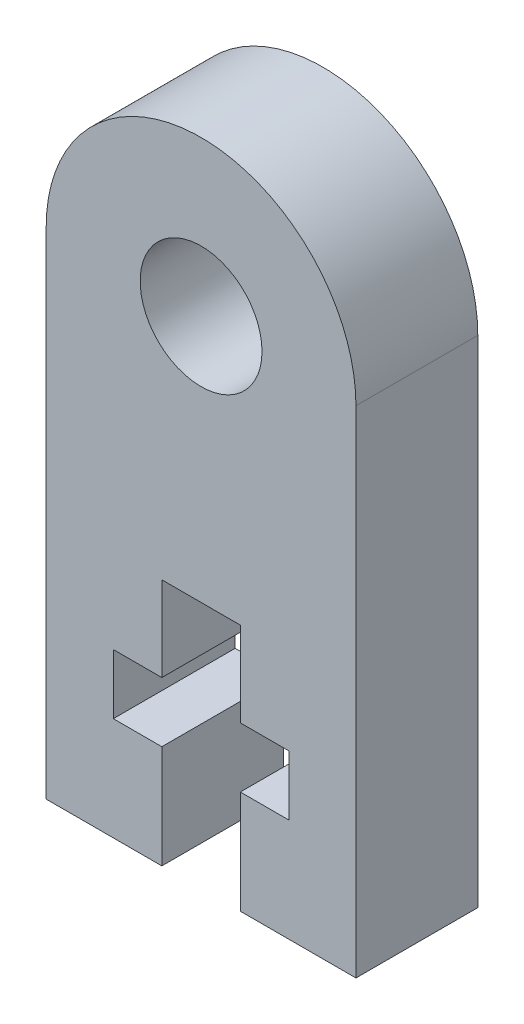
SolidWorks part; units mm, degrees
ref_plane "Front Plane" through (0, 0, 0) normal (0, 0, 1) x (1, 0, 0)
ref_plane "Top Plane" through (0, 0, 0) normal (0, 1, 0) x (1, 0, 0)
ref_plane "Right Plane" through (0, 0, 0) normal (1, 0, 0) x (0, 0, -1)
sketch "Sketch1" plane through (0, 0, 0) normal (0, 0, 1) x (1, 0, 0)
  line L0 (0, 0) -> (-2.086, 2.086) construction
  line L1 (0, 0) -> (0, 2.95) construction
  line L2 (-7.5, 0) -> (-7.5, -24)
  line L3 (-7.5, -24) -> (7.5, -24)
  line L4 (7.5, -24) -> (7.5, 0)
  line L5 (0, 0) -> (0, -24) construction
  circle A0 centre (0, 0) radius 2.95
  arc A1 (-7.5, 0) -> (7.5, 0) centre (0, 0) cw
  dimension "D1" = 5.9
  dimension "D4" = 45
  dimension "D5" = 24
  dimension "D6" = 15
extrude "Boss-Extrude1" add sketch "Sketch1" along normal blind 5.9
sketch "Sketch3" plane through (0, 0, 5.9) normal (0, 0, 1) x (1, 0, 0)
  line L0 (-7.5, -24) -> (7.5, -24) construction
  line L1 (-1.9, -24) -> (1.9, -24)
  line L2 (-1.9, -24) -> (-1.9, -19)
  line L3 (-1.9, -12) -> (1.9, -12)
  line L4 (1.9, -24) -> (1.9, -19)
  line L5 (0, -12) -> (0, 0) construction
  line L6 (1.9, -16.1) -> (4.25, -16.1)
  line L7 (-4.25, -16.1) -> (-1.9, -16.1)
  line L8 (-4.25, -16.1) -> (-4.25, -19)
  line L9 (-4.25, -19) -> (-1.9, -19)
  line L10 (4.25, -16.1) -> (4.25, -19)
  line L11 (-1.9, -16.1) -> (-1.9, -12)
  line L12 (1.9, -19) -> (4.25, -19)
  line L13 (1.9, -16.1) -> (1.9, -12)
  point P18 (-3.075, -19)
  dimension "D1" = 3.8
  dimension "D3" = 12
  dimension "D4" = 8.5
  dimension "D5" = 2.9
  dimension "D6" = 5
extrude "Cut-Extrude2" cut sketch "Sketch3" against normal through all
equation "\"smallPulleyTeeth\"= 15"
equation "\"largePulleyTeeth\"= 30"
equation "\"eighthThick\"= 2.9mm"
equation "\"sixteenthThick\" = 1.7mm"
equation "\"quarterThick\"=5.9mm"
equation "\"OD\" = 145mm"
equation "\"puckAngle\" = 60.5deg"
equation "\"puckDiam\" = 76.5mm"
equation "\"axlePress\" = 5.9mm"
equation "\"D1@Sketch1\"=\"axlePress\""
equation "\"D1@Boss-Extrude1\"=\"quarterThick\""
equation "\"press\" = 0.2mm"
equation "\"wheelClear\" = 0.3mm"
equation "\"10-32clear\" = 4.5mm"
equation "\"D1@Sketch3\"=\"8-32clear\"-\"press\""
equation "\"6-32clear\" = 3.3mm"
equation "\"8-32clear\" = 4.0mm"
equation "\"wheelHeight\" = 24mm"
equation "\"D5@Sketch1\"=\"wheelHeight\""
